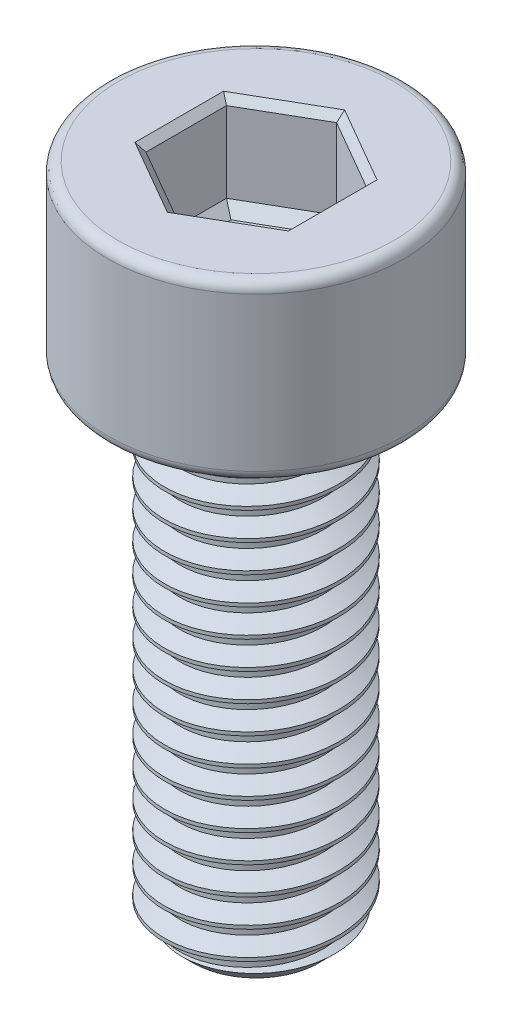
SolidWorks part; units mm, degrees
material "AISI Type A2 Tool Steel"
ref_plane "Front Plane" through (0, 0, 0) normal (0, 0, 1) x (1, 0, 0)
ref_plane "Top Plane" through (0, 0, 0) normal (0, 1, 0) x (1, 0, 0)
ref_plane "Right Plane" through (0, 0, 0) normal (1, 0, 0) x (0, 0, -1)
sketch "Sketch1" plane through (0, 0, 0) normal (0, 1, 0) x (1, 0, 0)
  circle A0 centre (0, 0) radius 2.5
  dimension "D1" = 5
extrude "Boss-Extrude1" add sketch "Sketch1" along normal blind 14
thread "Thread1" pitch 0.8 method cut profile "Thread Profile1" start angle 0, offset 1, length 0, pitch 0.8, diameter 5
ref_plane "Plane1" through (-2.5, 15, 0) normal (0, 0, 1) x (-1, 0, 0)
sketch "Thread Profile1" plane through (-2.5, 15, 0) normal (0, 0, 1) x (-1, 0, 0)
  line L0 (0, 0) -> (0, 0.8) construction
  line L11 (0, 0) -> (0, 0.7)
  line L12 (0, 0.7) -> (-0.433, 0.45)
  line L13 (-0.433, 0.45) -> (-0.433, 0.25)
  line L15 (-0.433, 0.25) -> (0, 0)
  line L17 (-0.433, 0.35) -> (0, 0.35) construction
  point P2 (0, 0)
  dimension "Pitch" = 0.8
  dimension "Profile_Angle" = 60
  dimension "Profile_Land" = 0.2
  dimension "Profile_Height" = 0.433
sketch "Sketch5" plane through (0, 14, 0) normal (0, 1, 0) x (1, 0, 0)
  circle A0 centre (0, 0) radius 4.25
  dimension "D1" = 8.5
extrude "Boss-Extrude2" add sketch "Sketch5" along normal blind 5
fillet "Fillet1" radius 0.3 2 edges at (0, 14, 4.25) (0, 19, 4.25)
sketch "Sketch6" plane through (0, 0, 0) normal (0, 0, 1) x (1, 0, 0)
  line L0 (0, 0) -> (0, 0.2882) construction
  line L1 (0, 0) -> (2.51, 0) construction
  line L2 (2.51, 0) -> (2.51, 0.7)
  line L3 (2.51, 0.7) -> (1.81, 0)
  line L4 (1.81, 0) -> (2.51, 0)
  dimension "D1" = 45
  dimension "D2" = 0.7
  dimension "D3" = 2.51
revolve "Cut-Revolve1" cut sketch "Sketch6" angle 360 about L0
sketch "Sketch7" plane through (0, 19, 0) normal (0, 1, 0) x (1, 0, 0)
  line L1 (0, 2.3094) -> (-2, 1.1547)
  line L2 (-2, 1.1547) -> (-2, -1.1547)
  line L3 (-2, -1.1547) -> (0, -2.3094)
  line L4 (0, -2.3094) -> (2, -1.1547)
  line L5 (2, -1.1547) -> (2, 1.1547)
  line L6 (2, 1.1547) -> (0, 2.3094)
  circle A0 centre (0, 0) radius 2 construction
  dimension "D1" = 4
extrude "Cut-Extrude1" cut sketch "Sketch7" against normal blind 2.5
chamfer "Chamfer1" distance 0.2 angle 45 6 edges at (-2, 19, 0) (-1, 19, 1.7321) (1, 19, 1.7321) (2, 19, 0) (1, 19, -1.7321) (-1, 19, -1.7321)
sketch "Sketch8" plane through (0, 16.5, 0) normal (0, 1, 0) x (1, 0, 0)
  line L1 (0, 2.3094) -> (-2, 1.1547)
  line L2 (-2, 1.1547) -> (-2, -1.1547)
  line L3 (-2, -1.1547) -> (0, -2.3094)
  line L4 (0, -2.3094) -> (2, -1.1547)
  line L5 (2, -1.1547) -> (2, 1.1547)
  line L6 (2, 1.1547) -> (0, 2.3094)
  circle A0 centre (0, 0) radius 2 construction
extrude "Cut-Extrude2" cut sketch "Sketch8" against normal blind 0.3 draft 45
